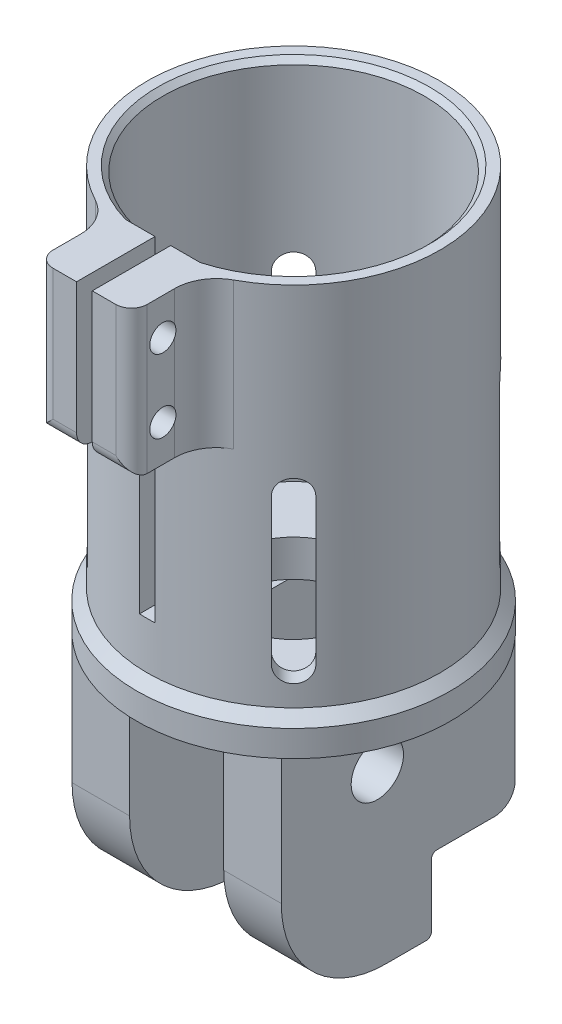
SolidWorks part; units mm, degrees
ref_plane "Front" through (0, 0, 0) normal (0, 0, 1) x (1, 0, 0)
ref_plane "Top" through (0, 0, 0) normal (0, 1, 0) x (1, 0, 0)
ref_plane "Right" through (0, 0, 0) normal (1, 0, 0) x (0, 0, -1)
sketch "Esquisse1" plane through (0, 0, 0) normal (0, 0, 1) x (1, 0, 0)
  line L0 (0, 0) -> (0, 39.8665) construction
  line L1 (-6, 0) -> (-15, 0)
  line L2 (-15, 0) -> (-15, 3.5)
  line L3 (-15, 3.5) -> (-14, 3.5)
  line L4 (-14, 3.5) -> (-14, 38.5)
  line L5 (-14, 38.5) -> (-12.5, 38.5)
  line L6 (-12.5, 38.5) -> (-12.5, 3.5)
  line L7 (-12.5, 3.5) -> (-6, 3.5)
  line L8 (-6, 3.5) -> (-6, 0)
  dimension "D1" = 25
  dimension "D2" = 28
  dimension "D3" = 35
  dimension "D4" = 3.5
  dimension "D5" = 30
  dimension "D6" = 12
revolve "Révolution1" add sketch "Esquisse1" angle 360 about L0
chamfer "Chanfrein1" distance 1 angle 45 1 edges at (0, 3.5, -15)
sketch "Esquisse2" plane through (0, 0, 0) normal (0, -1, 0) x (1, 0, 0)
  line L0 (0, 0) -> (0, 16.0415) construction
  line L1 (-10, 11.1803) -> (-4.5, 11.1803)
  line L2 (-10, 11.1803) -> (-10, -11.1803)
  line L3 (-10, -11.1803) -> (-4.5, -11.1803)
  line L4 (-4.5, 11.1803) -> (-4.5, -11.1803)
  line L5 (4.5, 11.1803) -> (4.5, -11.1803)
  line L6 (10, -11.1803) -> (4.5, -11.1803)
  line L7 (10, 11.1803) -> (10, -11.1803)
  line L8 (10, 11.1803) -> (4.5, 11.1803)
  circle A0 centre (0, 0) radius 15 construction
  dimension "D1" = 20
  dimension "D2" = 9
extrude "Boss.-Extru.1" add sketch "Esquisse2" along normal blind 22
fillet "Congé1" radius 10 2 edges at (-7.25, -22, 11.1803) (7.25, -22, 11.1803)
sketch "Esquisse3" plane through (-10, 0, 0) normal (-1, 0, 0) x (0, 0, 1)
  line L0 (-11.1803, 0) -> (11.1803, 0) construction
  line L1 (-11.1803, -22) -> (-3.1803, -22)
  line L2 (-11.1803, -22) -> (-11.1803, -15)
  line L3 (-11.1803, -15) -> (-3.1803, -15)
  line L4 (-3.1803, -22) -> (-3.1803, -15)
  dimension "D1" = 15
  dimension "D2" = 8
extrude "Enlèv. mat.-Extru.1" cut sketch "Esquisse3" against normal through all
fillet "Congé2" radius 2 2 edges at (7.25, -15, -11.1803) (-7.25, -15, -11.1803)
fillet "Congé3" radius 0.5 4 edges at (7.25, -22, -3.1803) (-7.25, -22, -3.1803) (7.25, -15, -3.1803) (-7.25, -15, -3.1803)
sketch "Esquisse4" plane through (0, 0, 0) normal (1, 0, 0) x (0, 0, -1)
  line L0 (11.1803, 0) -> (-11.1803, 0) construction
  line L1 (-15, 2.5) -> (-15, 0) construction
  circle A0 centre (-2, -5.5) radius 2.5
  dimension "D1" = 5.5
  dimension "D3" = 5
  dimension "D2" = 13
extrude "Enlèv. mat.-Extru.2" cut sketch "Esquisse4" against normal through all both and the other way through all
chamfer "Chanfrein2" distance 0.5 angle 45 1 edges at (0, 38.5, -12.5)
sketch "Esquisse6" plane through (0, 0, 0) normal (1, 0, 0) x (0, 0, -1)
  line L0 (14, 38.5) -> (-14, 38.5) construction
  line L1 (-20, 38.5) -> (-12.5, 38.5)
  line L2 (-20, 38.5) -> (-20, 24.5)
  line L3 (-20, 24.5) -> (-12.5, 24.5)
  line L4 (-12.5, 38.5) -> (-12.5, 24.5)
  dimension "D1" = 12.5
  dimension "D2" = 14
  dimension "D3" = 7.5
extrude "Boss.-Extru.2" add sketch "Esquisse6" along normal mid plane 9
fillet "Congé4" radius 4 2 edges at (4.5, 31.5, 13.2571) (-4.5, 31.5, 13.2571)
fillet "Congé5" radius 1.5 3 edges at (-4.5, 31.5, 20) (0, 24.5, 20) (4.5, 31.5, 20)
sketch "Esquisse5" plane through (0, 0, 0) normal (0, 0, 1) x (1, 0, 0)
  line L0 (14, 38.5) -> (-14, 38.5) construction
  line L1 (-0.75, 69) -> (0.75, 69)
  line L2 (-0.75, 69) -> (-0.75, 8)
  line L3 (-0.75, 8) -> (0.75, 8)
  line L4 (0.75, 69) -> (0.75, 8)
  line L5 (-0.75, 69) -> (0.75, 8) construction
  line L6 (-0.75, 8) -> (0.75, 69) construction
  line L7 (-10, 0) -> (10, 0) construction
  point P0 (0, 38.5)
  dimension "D1" = 8
  dimension "D2" = 1.5
extrude "Enlèv. mat.-Extru.3" cut sketch "Esquisse5" along normal through all
sketch "Esquisse7" plane through (0, 0, 0) normal (1, 0, 0) x (0, 0, -1)
  line L1 (-15.8666, 38.5) -> (-18.5, 38.5) construction
  circle A0 centre (-17, 28) radius 1.25
  circle A1 centre (-17, 35) radius 1.25
  dimension "D1" = 2.5
  dimension "D2" = 7
  dimension "D3" = 3.5
  dimension "D4" = 17
extrude "Enlèv. mat.-Extru.4" cut sketch "Esquisse7" against normal through all both and the other way through all
ref_plane "Plan1" through (9.8995, 0, -9.8995) normal (0.7071, 0, -0.7071) x (0, -1, 0)
sketch "Esquisse8" plane through (9.8995, 0, -9.8995) normal (0.7071, 0, -0.7071) x (0, -1, 0)
  line L0 (-7, 0) -> (-21, 0) construction
  line L1 (-7, -1.5) -> (-21, -1.5)
  line L2 (-7, 1.5) -> (-21, 1.5)
  line L3 (0, 0.8346) -> (0, 14.9768) construction
  arc A0 (-7, -1.5) -> (-7, 1.5) centre (-7, 0) ccw
  arc A1 (-21, 1.5) -> (-21, -1.5) centre (-21, 0) ccw
  point P3 (-14, 0)
  point P8 (-22.5, 0)
  point P9 (-5.5, 0)
  dimension "D1" = 3
  dimension "D2" = 17
  dimension "D3" = 5.5
extrude "Enlèv. mat.-Extru.5" cut sketch "Esquisse8" against normal up to next
pattern_circular "Répétition circulaire1" count 4 over 360 about axis through (0, 0, 0) along (0, -1, 0) of "Enlèv. mat.-Extru.5"
sketch "Sketch1" [suppressed] plane through (10, 0, 0) normal (1, 0, 0) x (0, 0, -1)
  line L3 (3.6803, -15) -> (9.1803, -15) construction
  arc A0 (-11.1803, -12) -> (-1.1803, -22) centre (-1.1803, -12) ccw construction
  arc A3 (9.1803, -15) -> (11.1803, -13) centre (9.1803, -13) ccw construction
  spline S0 degree 3 poles (-11.1803, 0) (-11.191, -5.1891) (-11.2237, -9.2177) (-11.1391, -15.2738) (-9.5726, -17.3228) (-7.1765, -20.526) (-4.0215, -21.825) (-0.1566, -22.0711) (2.1137, -21.9948) (2.8523, -22.0103) (3.1957, -21.773) (3.1652, -20.8099) (3.1781, -15.9449) (3.1765, -15.2396) (3.4805, -14.9942) (4.2886, -14.9952) (6.108, -15.0079) (9.1803, -15) knots 0 0 0 0 0.173161 0.216262 0.407156 0.451485 0.615221 0.644912 0.718702 0.731529 0.760358 0.771751 0.834073 0.846716 0.885537 0.901351 1 1 1 1
sketch "Sketch3" plane through (10, 0, 0) normal (1, 0, 0) x (0, 0, -1)
  line L0 (3.6803, -15) -> (9.1803, -15) construction
  line L1 (3.1803, -21.5) -> (3.1803, -15.5) construction
  line L2 (2.6803, -22) -> (-1.1803, -22) construction
  line L3 (-11.1803, -12) -> (-11.1803, 0) construction
  line L4 (3.6803, -15) -> (9.1803, -15)
  line L5 (3.1803, -21.5) -> (3.1803, -15.5)
  line L6 (2.6803, -22) -> (-1.1803, -22)
  line L7 (-11.1803, -12) -> (-11.1803, 0)
  line L8 (5.4303, -17.25) -> (9.1803, -17.25) construction
  line L9 (5.4303, -21.5) -> (5.4303, -17.25) construction
  line L10 (2.6803, -24.25) -> (-1.1803, -24.25) construction
  line L11 (-13.4303, -12) -> (-13.4303, 0) construction
  arc A0 (3.6803, -15) -> (3.1803, -15.5) centre (3.6803, -15.5) ccw construction
  arc A1 (2.6803, -22) -> (3.1803, -21.5) centre (2.6803, -21.5) ccw construction
  arc A2 (-11.1803, -12) -> (-1.1803, -22) centre (-1.1803, -12) ccw construction
  arc A3 (3.6803, -15) -> (3.1803, -15.5) centre (3.6803, -15.5) ccw
  arc A4 (2.6803, -22) -> (3.1803, -21.5) centre (2.6803, -21.5) ccw
  arc A5 (-11.1803, -12) -> (-1.1803, -22) centre (-1.1803, -12) ccw
  arc A6 (5.4303, -17.25) -> (5.4303, -17.25) centre (5.4303, -17.25) ccw construction
  arc A7 (2.6803, -24.25) -> (5.4303, -21.5) centre (2.6803, -21.5) ccw construction
  arc A8 (-13.4303, -12) -> (-1.1803, -24.25) centre (-1.1803, -12) ccw construction
sketch "Pin Path" plane through (10, 0, 0) normal (1, 0, 0) x (0, 0, -1)
  line L0 (5.4303, -17.25) -> (9.1803, -17.25) construction
  line L1 (5.4303, -21.5) -> (5.4303, -17.25) construction
  line L2 (2.6803, -24.25) -> (-1.1803, -24.25) construction
  line L3 (-13.4303, -12) -> (-13.4303, 0) construction
  arc A0 (2.6803, -24.25) -> (5.4303, -21.5) centre (2.6803, -21.5) ccw construction
  arc A1 (-13.4303, -12) -> (-1.1803, -24.25) centre (-1.1803, -12) ccw construction
  spline S0 degree 3 poles (-13.4303, 0) (-13.4303, -4) (-13.4303, -8.5311) (-13.4303, -13.5932) (-13.0438, -15.1895) (-12.7011, -16.1972) (-12.4979, -16.6879) (-10.6884, -21.0563) (-6.8642, -23.837) (-2.1507, -24.2115) (-2.0432, -24.2201) (-1.8278, -24.2343) (-1.5041, -24.25) (-0.0014, -24.25) (1.5127, -24.25) (3.038, -24.25) (3.3963, -24.1632) (3.6226, -24.0863) (3.7327, -24.0407) (4.4156, -23.7578) (4.9382, -23.2352) (5.221, -22.5524) (5.2666, -22.4422) (5.3436, -22.216) (5.4303, -21.8577) (5.4303, -20.2446) (5.4303, -18.7321) (5.4303, -17.3201) (5.4856, -17.25) (6.7359, -17.25) (7.9674, -17.25) (9.1803, -17.25) knots 0 0 0 0 0.257586 0.291786 0.325986 0.360185 0.360185 0.360185 0.6348 0.6348 0.6348 0.641749 0.648697 0.655646 0.738517 0.746195 0.753872 0.76155 0.76155 0.76155 0.80673 0.80673 0.80673 0.814407 0.822085 0.829762 0.918282 0.919486 0.92069 0.921894 1 1 1 1 weights 1 1 1 1 1 1 1 0.901892 0.901892 1 1 1 1 1 1 1 1 1 1 0.949253 0.949253 1 1 1 1 1 1 1 1 1 1 1
